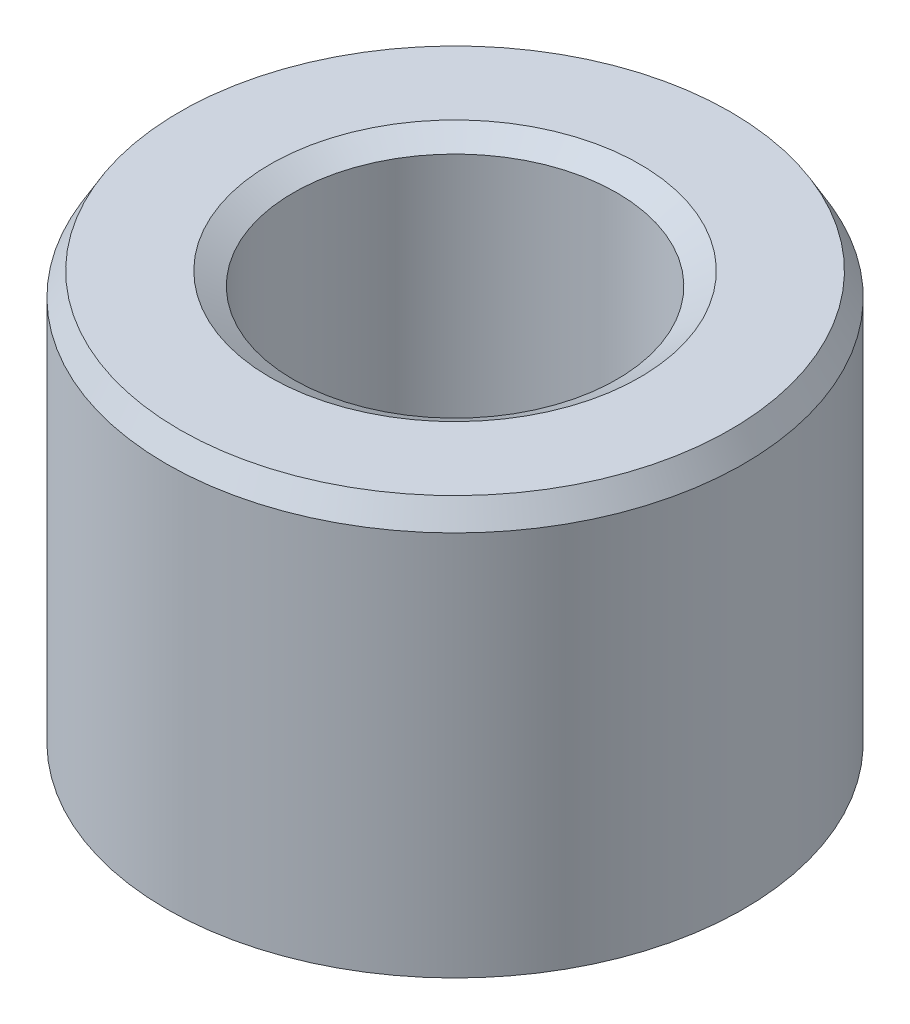
SolidWorks part; units mm, degrees
ref_plane "Front Plane" through (0, 0, 0) normal (0, 0, 1) x (1, 0, 0)
ref_plane "Top Plane" through (0, 0, 0) normal (0, 1, 0) x (1, 0, 0)
ref_plane "Right Plane" through (0, 0, 0) normal (1, 0, 0) x (0, 0, -1)
sketch "Sketch1" plane through (0, 0, 0) normal (0, 1, 0) x (1, 0, 0)
  circle A0 centre (0, 0) radius 22.5
  dimension "SLEEVE_OD" = 45
extrude "Boss-Extrude1" add sketch "Sketch1" along normal blind 32.8723
sketch "Sketch2" plane through (0, 0, 0) normal (0, 1, 0) x (1, 0, 0)
  circle A0 centre (0, 0) radius 12.6112
  dimension "BORE_D" = 25.2224
extrude "Cut-Extrude1" cut sketch "Sketch2" along normal through all
chamfer "Chamfer1" distance 1.7922 angle 30 4 edges at (0, 32.8723, 12.6112) (0, 0, 12.6112) (0, 0, 22.5) (0, 32.8723, 22.5) first distance on face at (0, 32.8723, 12.6112) first distance on face at (0, 0, 12.6112) first distance on face at (0, 32.8723, 22.5)
